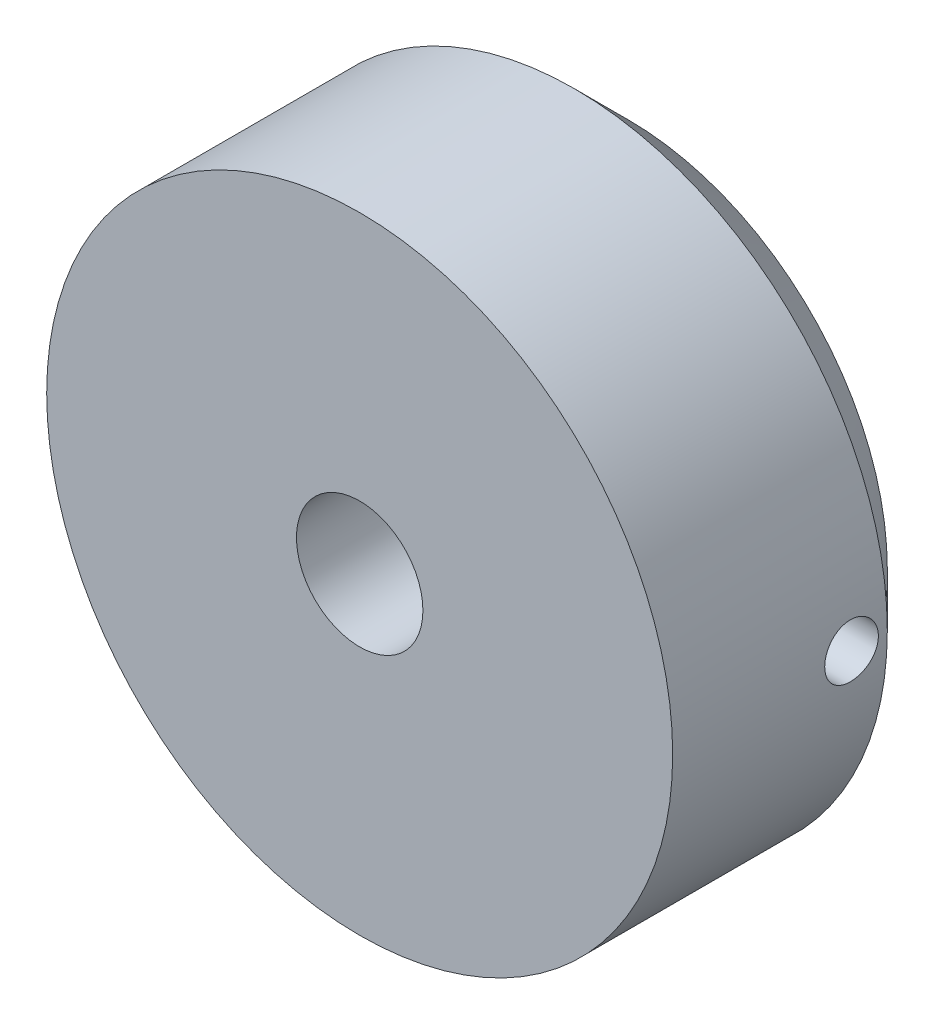
SolidWorks part; units mm, degrees
ref_plane "Front Plane" through (0, 0, 0) normal (0, 0, 1) x (1, 0, 0)
ref_plane "Top Plane" through (0, 0, 0) normal (0, 1, 0) x (1, 0, 0)
ref_plane "Right Plane" through (0, 0, 0) normal (1, 0, 0) x (0, 0, -1)
ref_axis "Z" through (0, 0, 543.0939) along (0, 0, -1)
ref_axis "X" through (17.0818, 0, 0) along (-1, 0, 0)
ref_axis "Y" through (0, 33, 0) along (0, -1, 0)
sketch "Sketch1" plane through (0, 0, 0) normal (0, 0, 1) x (1, 0, 0)
  circle A0 centre (0, 0) radius 17.5
  circle A1 centre (0, 0) radius 3.535
  dimension "D1" = 35
  dimension "D2" = 7.07
extrude "Boss-Extrude1" add sketch "Sketch1" against normal blind 5 and the other way blind 10
sketch "Sketch2" plane through (0, 0, 0) normal (0, 1, 0) x (1, 0, 0)
  line L0 (-33, 0) -> (33, 0) construction
  line L1 (0, -8.25) -> (0, 8.25) construction
  circle A0 centre (0, 0) radius 1.5
  dimension "D1" = 3
extrude "Cut-Extrude1" cut sketch "Sketch2" against normal through all
sketch "Sketch3" plane through (0, 0, 0) normal (1, 0, 0) x (0, 0, -1)
  circle A0 centre (0, 0) radius 1.5
  dimension "D1" = 3
extrude "Cut-Extrude2" cut sketch "Sketch3" along normal through all
chamfer "Chamfer1" distance 3 angle 45 1 edges at (17.5, 0, -5)
sketch "Sketch4" plane through (0, 0, 0) normal (0, 0, 1) x (1, 0, 0)
  circle A0 centre (0, 0) radius 3.535
  circle A2 centre (0, 0) radius 3.535 construction
  circle A3 centre (0, 0) radius 11.5
  dimension "D1" = 23
extrude "Boss-Extrude2" add sketch "Sketch4" along normal up to surface and the other way up to surface up to face at (17.5, 0, 10) other way up to face at (14.5, 0, -5)
equation "\"EyeDiameter\" = 35"
equation "\"BasePlaneDistance\" = \"EyeDiameter\"/2+19.84"
equation "\"EyeClearance\" = 2"
equation "\"EyeOD\"= \"EyeDiameter\""
equation "\"D1@Sketch1\"=\"EyeOD\""
equation "\"D2@Sketch1\"= 7.07"
equation "\"pinHoleDiameter\"= 3"
equation "\"D1@Sketch2\"=\"pinHoleDiameter\""
equation "\"D1@Sketch3\"=\"pinHoleDiameter\""
equation "\"D1@Sketch4\"=\"EyeDiameter\"-12"
